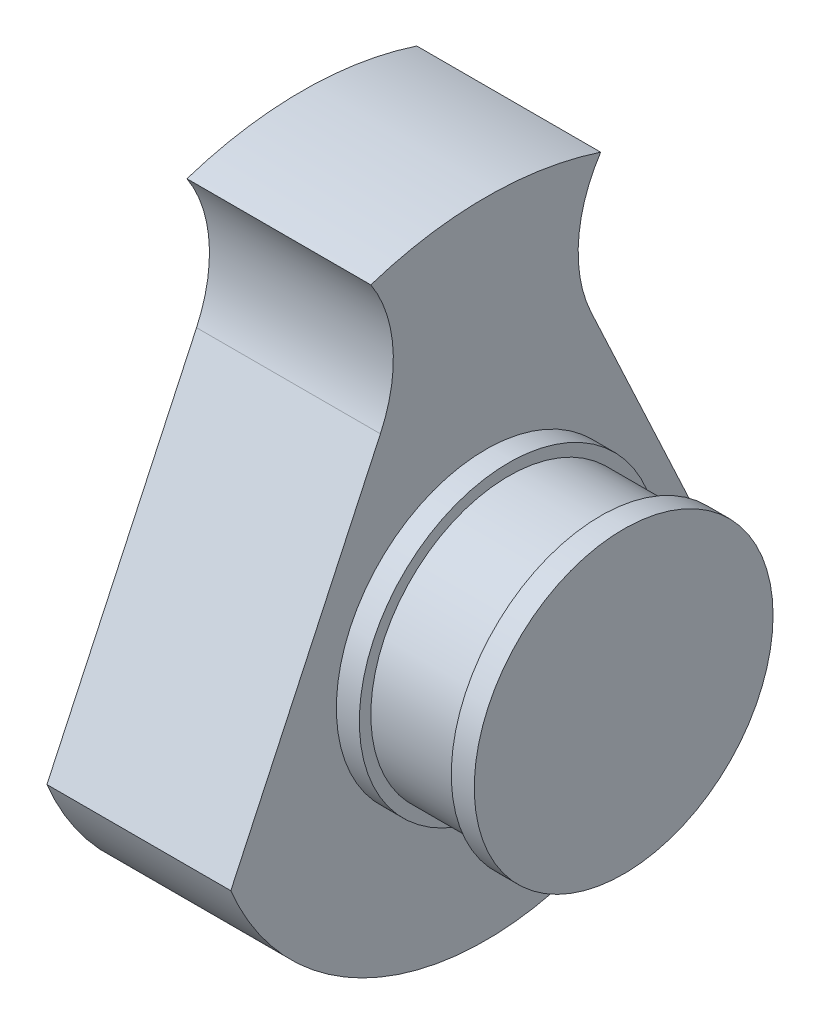
SolidWorks part; units mm, degrees
material "AISI Type A2 Tool Steel"
ref_plane "Front Plane" through (0, 0, 0) normal (0, 0, 1) x (1, 0, 0)
ref_plane "Top Plane" through (0, 0, 0) normal (0, 1, 0) x (1, 0, 0)
ref_plane "Right Plane" through (0, 0, 0) normal (1, 0, 0) x (0, 0, -1)
sketch "Sketch2" plane through (0, 0, 0) normal (1, 0, 0) x (0, 0, -1)
  circle A0 centre (0, 0) radius 50.8
  dimension "D1" = 101.6
extrude "Boss-Extrude1" add sketch "Sketch2" along normal mid plane 25.4
sketch "Sketch3" plane through (12.7, 0, 0) normal (1, 0, 0) x (0, 0, -1)
  line L0 (0, 0) -> (-15.875, 48.2558) construction
  line L1 (-15.875, 48.2558) -> (37.8761, -33.8533) construction
  line L2 (0, 0) -> (0, 50.8) construction
  line L3 (-15.875, 48.2558) -> (0, 48.2558) construction
  line L4 (-14.5484, 29.7711) -> (-41.8552, -28.7886)
  arc A0 (-15.875, 48.2558) -> (-14.5484, 29.7711) centre (-31.8135, 37.822) cw
  circle A1 centre (0, 0) radius 50.8 construction
  circle A3 centre (0, 0) radius 50.8
  arc A4 (-15.875, 48.2558) -> (-41.8552, -28.7886) centre (0, 0) ccw
  point P2 (-27.5319, 0.428)
  point P9 (-49.3585, -11.1598)
  point P10 (-27.5816, 1.0439)
  point P11 (-46.7528, -19.8699)
  dimension "D3" = 19.05
  dimension "D2" = 15
  dimension "D4" = 15.875
  dimension "D5" = 25
  dimension "D1" = 0
extrude "Cut-Extrude1" cut sketch "Sketch3" against normal through all
mirror "Mirror1" about plane through (0, 0, 0) normal (0, 0, 1) of "Cut-Extrude1"
sketch "Sketch4" plane through (12.7, 0, 0) normal (1, 0, 0) x (0, 0, -1)
  line L2 (41.8552, -28.7886) -> (14.5484, 29.7711)
  line L3 (41.8552, -28.7886) -> (35.2139, -14.5462)
  line L4 (-14.5484, 29.7711) -> (-41.8552, -28.7886)
  line L5 (-35.2139, -14.5462) -> (-41.8552, -28.7886)
  arc A0 (-35.2139, -14.5462) -> (35.2139, -14.5462) centre (0, 0) ccw
  arc A7 (-41.8552, -28.7886) -> (41.8552, -28.7886) centre (0, 0) ccw
  arc A8 (15.875, 48.2558) -> (14.5484, 29.7711) centre (31.8135, 37.822) ccw
  arc A9 (15.875, 48.2558) -> (-15.875, 48.2558) centre (0, 0) ccw
  arc A10 (-14.5484, 29.7711) -> (-15.875, 48.2558) centre (-31.8135, 37.822) ccw
  arc A15 (-41.8552, -28.7886) -> (41.8552, -28.7886) centre (0, 0) ccw
  dimension "D2" = 38.1
  dimension "D1" = 0
extrude "Cut-Extrude2" cut sketch "Sketch4" against normal through all
sketch "Sketch5" plane through (12.7, 0, 0) normal (1, 0, 0) x (0, 0, -1)
  circle A0 centre (0, 0) radius 9.525
  circle A1 centre (0, 0) radius 6.35 construction
  dimension "D1" = 12.7
  dimension "D2" = 19.05
sketch "Sketch7" plane through (12.7, 0, 0) normal (1, 0, 0) x (0, 0, -1)
  line L0 (-16.1607, 0) -> (-8.7581, 15.875)
  line L1 (-8.7581, 15.875) -> (8.7581, 15.875)
  line L2 (8.7581, 15.875) -> (16.1607, 0)
  line L3 (16.1607, 0) -> (8.7581, -15.875)
  line L4 (8.7581, -15.875) -> (-8.7581, -15.875)
  line L5 (-8.7581, -15.875) -> (-16.1607, 0)
  line L6 (-16.1607, 0) -> (0, 0) construction
  line L7 (0, 0) -> (16.1607, 0) construction
  line L8 (0, -15.875) -> (0, 0) construction
  line L9 (0, 0) -> (0, 15.875) construction
  line L10 (-35.2139, -14.5462) -> (-14.5484, 29.7711) construction
  point P12 (-9.4379, -15.5167)
  dimension "D1" = 31.75
extrude "Cut-Extrude4" cut sketch "Sketch7" against normal blind 9.525
sketch "Sketch9" plane through (3.175, 0, 0) normal (1, 0, 0) x (0, 0, -1)
  line L7 (-16.0206, 0) -> (-8.6772, -15.748)
  line L8 (-8.6772, -15.748) -> (8.6772, -15.748)
  line L9 (8.6772, -15.748) -> (16.0206, 0)
  line L10 (16.0206, 0) -> (8.6772, 15.748)
  line L11 (8.6772, 15.748) -> (-8.6772, 15.748)
  line L12 (-8.6772, 15.748) -> (-16.0206, 0)
  line L13 (-16.1607, 0) -> (-8.7581, -15.875)
  line L14 (-8.7581, -15.875) -> (8.7581, -15.875)
  line L15 (8.7581, -15.875) -> (16.1607, 0)
  line L16 (16.1607, 0) -> (8.7581, 15.875)
  line L17 (8.7581, 15.875) -> (-8.7581, 15.875)
  line L18 (-8.7581, 15.875) -> (-16.1607, 0)
  line L19 (-16.1607, 0) -> (-8.7581, -15.875) construction
  line L20 (-8.7581, -15.875) -> (8.7581, -15.875) construction
  line L21 (8.7581, -15.875) -> (16.1607, 0) construction
  line L22 (16.1607, 0) -> (8.7581, 15.875) construction
  line L23 (8.7581, 15.875) -> (-8.7581, 15.875) construction
  line L24 (-8.7581, 15.875) -> (-16.1607, 0) construction
  point P0 (13.9897, 0)
  point P11 (0, 0)
  dimension "D1" = 0
  dimension "D2" = 0.127
extrude "Boss-Extrude2" add sketch "Sketch9" along normal up to surface (9.525 mm away) separate body up to face at (12.7, 0, 0)
mirror "Mirror2" about plane through (0, 0, 0) normal (1, 0, 0) of "Cut-Extrude4"
mirror "Mirror3" about plane through (0, 0, 0) normal (1, 0, 0) of bodies 108
sketch "Sketch10" plane through (12.7, 0, 0) normal (1, 0, 0) x (0, 0, -1)
  circle A0 centre (0, 0) radius 20.6375
  dimension "D1" = 41.275
extrude "Boss-Extrude3" add sketch "Sketch10" along normal blind 3.175 separate body
sketch "Sketch11" plane through (15.875, 0, 0) normal (1, 0, 0) x (0, 0, -1)
  circle A0 centre (0, 0) radius 19.05
  dimension "D1" = 38.1
extrude "Boss-Extrude4" add sketch "Sketch11" along normal blind 12.7 separate body
sketch "Sketch12" plane through (28.575, 0, 0) normal (1, 0, 0) x (0, 0, -1)
  circle A0 centre (0, 0) radius 20.6375 construction
  circle A1 centre (0, 0) radius 20.6375
extrude "Boss-Extrude5" add sketch "Sketch12" along normal blind 3.175 separate body
